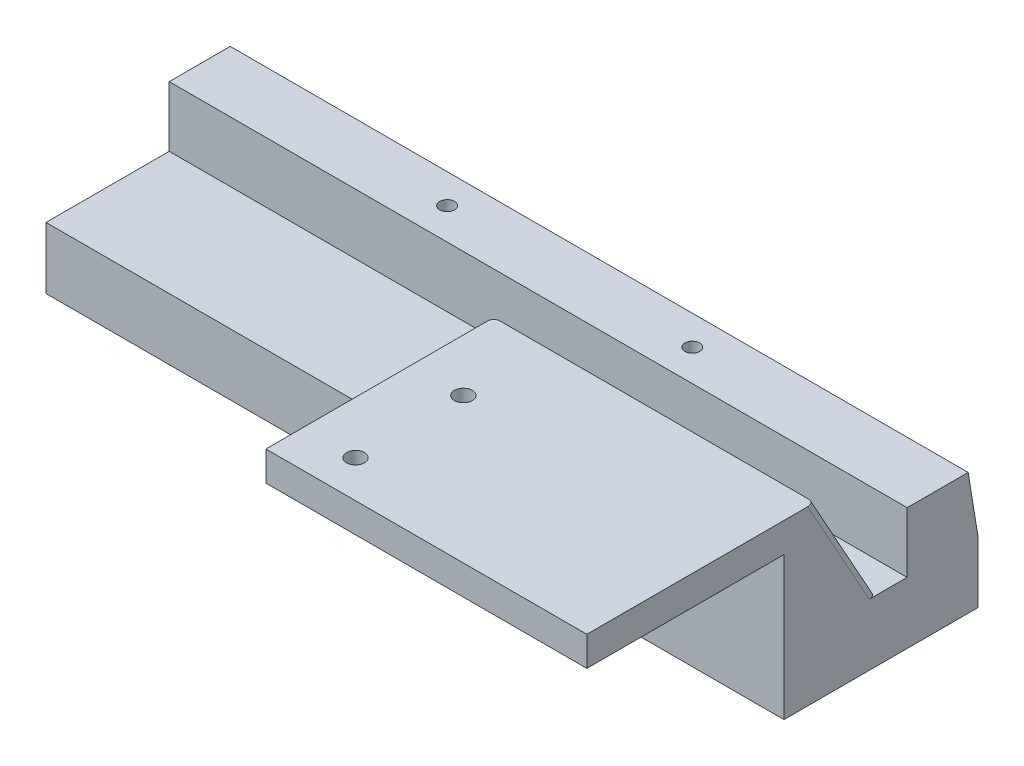
SolidWorks part; units mm, degrees
ref_plane "Płaszczyzna przednia" through (0, 0, 0) normal (0, 0, 1) x (1, 0, 0)
ref_plane "Płaszczyzna górna" through (0, 0, 0) normal (0, 1, 0) x (1, 0, 0)
ref_plane "Płaszczyzna prawa" through (0, 0, 0) normal (1, 0, 0) x (0, 0, -1)
sketch "Szkic1" plane through (0, 0, 0) normal (0, 0, 1) x (1, 0, 0)
  line L1 (-58.3066, 32.0248) -> (61.4934, 32.0248)
  line L2 (-58.3066, 32.0248) -> (-58.3066, 22.0248)
  line L3 (-58.3066, 22.0248) -> (61.4934, 22.0248)
  line L4 (61.4934, 32.0248) -> (61.4934, 22.0248)
  dimension "D1" = 119.8
  dimension "D2" = 10
extrude "Dodanie-wyciągnięcie2" add sketch "Szkic1" along normal blind 30 contours L2 L3 L4 L1
sketch "Szkic21" plane through (0, 32.0248, 0) normal (0, 1, 0) x (1, 0, 0)
  line L0 (61.4934, -30) -> (61.4934, 0) construction
  line L1 (-58.3066, 0) -> (61.4934, 0)
  line L2 (-58.3066, 0) -> (-58.3066, -10)
  line L3 (-58.3066, -10) -> (61.4934, -10)
  line L4 (61.4934, 0) -> (61.4934, -10)
extrude "Dodanie-wyciągnięcie3" add sketch "Szkic21" along normal blind 9.8
sketch "Szkic22" plane through (0, 22.0248, 0) normal (0, -1, 0) x (1, 0, 0)
  line L0 (-58.3066, 4.88) -> (-18.3066, 4.88) construction
  line L1 (-58.3066, 30) -> (-58.3066, 0) construction
  line L2 (-18.3066, 4.88) -> (21.4934, 4.88) construction
  line L3 (21.4934, 4.88) -> (61.4934, 4.88) construction
  line L4 (61.4934, 30) -> (61.4934, 0) construction
  line L5 (1.9729, 4.88) -> (1.9729, 0) construction
  line L6 (-58.3066, 0) -> (61.4934, 0) construction
hole_wizard "Pogłębienie walcowe pod M2 wkręt do części metalowych z łbem stożkowym ściętym2" positions "Szkic23" profile "Szkic24" counterbore size "M2" standard "Ansi Metric" end condition through all
sketch "Szkic23" plane through (0, 22.0248, 0) normal (0, -1, 0) x (-1, 0, 0)
  point P0 (-21.4934, -4.88)
  point P3 (18.3066, -4.88)
sketch "Szkic24" plane through (21.4934, 22.0248, 4.88) normal (1, 0, 0) x (0, 0, -1)
  line L0 (0, 0) -> (0, 19.8)
  line L1 (0, 19.8) -> (1.2, 19.8)
  line L3 (1.2, 19.8) -> (1.2, 1.6)
  line L4 (1.2, 1.6) -> (2.5, 1.6)
  line L5 (2.5, 1.6) -> (2.5, 0)
  line L7 (2.5, 0) -> (0, 0)
  line L11 (0, -6.35) -> (0, 107.95) construction
  dimension "Średnica otworu na wylot" = 2.4
  dimension "Głębokość otworu na wylot" = 19.8
  dimension "Średnica pogłębienia walcowego" = 5
  dimension "Głębokość pogłębienia walcowego" = 1.6
sketch "Szkic28" plane through (0, 22.0248, 0) normal (0, -1, 0) x (1, 0, 0)
  line L0 (38.4934, 0) -> (38.4934, 15) construction
  line L1 (-58.3066, 0) -> (61.4934, 0) construction
  line L2 (38.4934, 15) -> (61.4934, 15) construction
  line L3 (61.4934, 30) -> (61.4934, 0) construction
  line L4 (-58.3066, 30) -> (61.4934, 30) construction
  circle A0 centre (38.4934, 15) radius 11.1
  dimension "D1" = 15
extrude "Wytnij-wyciągnięcie1" cut sketch "Szkic28" against normal blind 7.2
sketch "Szkic31" plane through (61.4934, 0, 0) normal (1, 0, 0) x (0, 0, -1)
  line L0 (-10, 32.0248) -> (-10, 71.9248)
  line L2 (0, 41.2325) -> (0, 32.0248)
  line L6 (0, 41.8248) -> (0, 22.0248) construction
  line L8 (0, 32.0248) -> (1.5, 32.0248)
  line L10 (-10, 32.0248) -> (1.5, 32.0248)
  line L12 (-10, 71.9248) -> (-5, 71.9248)
  line L13 (-5, 71.9248) -> (1.5, 32.0248)
  line L14 (-0.4105, 43.7521) -> (0.2752, 39.543)
  line L15 (0.2752, 39.543) -> (3.3905, 40.0505)
  line L16 (3.3905, 40.0505) -> (-0.4105, 43.7521)
  line M5 (0, 22.0248) -> (0, 41.8248)
  line M6 (0, 41.8248) -> (-10, 41.8248)
extrude "Wytnij-wyciągnięcie4" cut sketch "Szkic31" against normal blind 124.8 contours L13 M6 M5 region at (61.4934, 41.6274, 0.0322)
extrude "Dodanie-wyciągnięcie5" add sketch "Szkic31<5>" against normal blind 119.8 contours L13 L8 M5 region at (61.4934, 35.0941, -0.5)
sketch "Szkic31<5>" plane through (61.4934, 0, 0) normal (1, 0, 0) x (0, 0, -1) same geometry as "Szkic31"
sketch "Szkic34" plane through (0, 0, 0) normal (0, 0, -1) x (-1, 0, 0)
  line L1 (-61.4934, 32.0248) -> (58.3066, 32.0248)
  line L2 (-61.4934, 32.0248) -> (-61.4934, 22.0248)
  line L3 (-61.4934, 22.0248) -> (58.3066, 22.0248)
  line L4 (58.3066, 32.0248) -> (58.3066, 22.0248)
extrude "Dodanie-wyciągnięcie6" add sketch "Szkic34" along normal blind 1.5
sketch "Szkic37" plane through (0, 32.0248, 0) normal (0, 1, 0) x (1, 0, 0)
  line L1 (61.4934, -30) -> (9.3934, -30)
  line L2 (61.4934, -30) -> (61.4934, -25)
  line L3 (61.4934, -25) -> (9.3934, -25)
  line L4 (9.3934, -30) -> (9.3934, -25)
extrude "Dodanie-wyciągnięcie8" add sketch "Szkic37" along normal blind 18
sketch "Szkic38" plane through (0, 0, 30) normal (0, 0, 1) x (1, 0, 0)
  line L0 (61.4934, 50.0248) -> (61.4934, 22.0248) construction
  line L1 (9.3934, 50.0248) -> (61.4934, 50.0248)
  line L2 (9.3934, 50.0248) -> (9.3934, 45.2248)
  line L3 (9.3934, 45.2248) -> (61.4934, 45.2248)
  line L4 (61.4934, 50.0248) -> (61.4934, 45.2248)
extrude "Dodanie-wyciągnięcie11" add sketch "Szkic38" along normal blind 32
sketch "Szkic40" plane through (0, 45.2248, 0) normal (0, -1, 0) x (1, 0, 0)
  line L0 (9.3934, 35.85) -> (61.4934, 35.85) construction
  line L1 (9.3934, 62) -> (9.3934, 30) construction
  line L2 (61.4934, 62) -> (61.4934, 30) construction
  line L3 (9.3934, 30) -> (61.4934, 30) construction
  line L4 (49.3934, 35.85) -> (49.3934, 30) construction
  line L5 (9.3934, 58.35) -> (61.4934, 58.35) construction
  line L6 (9.3934, 62) -> (61.4934, 62) construction
  line L7 (9.3934, 47.1) -> (61.4934, 47.1) construction
  line L8 (42.4023, 35.85) -> (47.4023, 35.85)
  line L9 (42.4023, 35.85) -> (42.4023, 34.35)
  line L10 (42.4023, 34.35) -> (47.4023, 34.35)
  line L11 (47.4023, 35.85) -> (47.4023, 34.35)
  line L12 (32.3245, 58.35) -> (32.3245, 47.1) construction
  line L13 (32.3245, 47.1) -> (32.3245, 35.85) construction
  dimension "D1" = 5.85
  dimension "D2" = 12.1
  dimension "D3" = 3.65
ref_plane "Płaszczyzna1" through (0, 43.2248, 0) normal (0, -1, 0) x (-1, 0, 0)
sketch "Szkic41" plane through (0, 43.2248, 0) normal (0, -1, 0) x (-1, 0, 0)
  line L0 (-42.4023, -34.35) -> (-47.4023, -34.35) construction
  line L1 (-46.7591, -34.35) -> (-43.0456, -34.35)
  line L2 (-46.7591, -34.35) -> (-46.7591, -35.85)
  line L3 (-46.7591, -35.85) -> (-43.0456, -35.85)
  line L4 (-43.0456, -34.35) -> (-43.0456, -35.85)
  line L5 (-42.4023, -35.85) -> (-47.4023, -35.85) construction
  line L12 (-47.4023, -35.1) -> (-46.7591, -35.1) construction
  line L13 (-47.4023, -35.85) -> (-47.4023, -34.35) construction
  line L14 (-43.0456, -35.1) -> (-42.4023, -35.1) construction
  line L15 (-42.4023, -35.85) -> (-42.4023, -34.35) construction
loft "Wyciągnięcie po profilach5" add profiles "Szkic40", "Szkic41"
fillet "Zaokrąglenie5" radius 0.5 8 edges
pattern_linear "Szyk liniowy2" count 2 spacing 24.2 along (0, 0, 1) of "Zaokrąglenie5", "Wyciągnięcie po profilach5"
sketch "Szkic43" plane through (0, 45.2248, 0) normal (0, -1, 0) x (1, 0, 0)
  line L0 (9.3934, 55.95) -> (17.8934, 55.95) construction
  line L1 (9.3934, 62) -> (9.3934, 30) construction
  line L3 (9.3934, 38.45) -> (17.8934, 38.45) construction
  line L4 (17.8934, 62) -> (17.8934, 55.95) construction
  line L7 (9.3934, 62) -> (61.4934, 62) construction
  line L8 (17.8934, 55.95) -> (17.8934, 38.45) construction
  line L9 (17.8934, 38.45) -> (17.8934, 30) construction
  line L10 (9.3934, 30) -> (61.4934, 30) construction
  line L11 (17.8934, 55.95) -> (61.4934, 55.95) construction
  line L12 (61.4934, 62) -> (61.4934, 30) construction
  line L13 (17.8934, 38.45) -> (61.4934, 38.45) construction
  line L14 (46.8771, 35.85) -> (42.9276, 35.85) construction
  line L15 (44.9023, 35.85) -> (44.9023, 38.45)
  line L16 (44.9023, 38.45) -> (44.9023, 55.95)
  line L17 (44.9023, 55.95) -> (44.9023, 58.55)
  line L18 (42.9276, 58.55) -> (46.8771, 58.55) construction
  dimension "D1" = 8.45
  dimension "D2" = 43.6
  dimension "18.1" = 17.5
hole_wizard "Otwór pod śrubę M2.51" positions "Szkic44" profile "Szkic45" hole size "M2.5" standard "ISO" end condition through all
sketch "Szkic44" plane through (0, 45.2248, 0) normal (0, -1, 0) x (-1, 0, 0)
  point P0 (-17.8934, -38.45)
  point P3 (-17.8934, -55.95)
sketch "Szkic45" plane through (17.8934, 45.2248, 38.45) normal (1, 0, 0) x (0, 0, -1)
  line L0 (0, 0) -> (0, 4.8)
  line L1 (0, 4.8) -> (1.45, 4.8)
  line L2 (1.45, 4.8) -> (1.45, 0)
  line L5 (1.45, 0) -> (0, 0)
  line L11 (0, -6.35) -> (0, 107.95) construction
  dimension "Średnica otworu na wylot" = 2.9
  dimension "Głębokość otworu na wylot" = 4.8
sketch "Szkic52" plane through (61.4934, 0, 0) normal (1, 0, 0) x (0, 0, -1)
  line L0 (-25, 50.0248) -> (-15, 32.0248)
  line L1 (-25, 32.0248) -> (-10, 32.0248) construction
rib "Żebro7" sketch "Szkic52" sketch "Szkic52" thickness 3 extrusion direction parallel to sketch draft on no parameters "D1"=3
fillet "Zaokrąglenie7" radius 1 2 edges at (61.4934, 41.0248, 20) (58.4934, 41.0248, 20)
pattern_linear "Szyk liniowy6" count 5 spacing 12.25 along (-1, 0, 0) of "Żebro7", "Zaokrąglenie7"
fillet "Zaokrąglenie8" radius 1 1 edges at (9.3934, 41.0248, 25)
